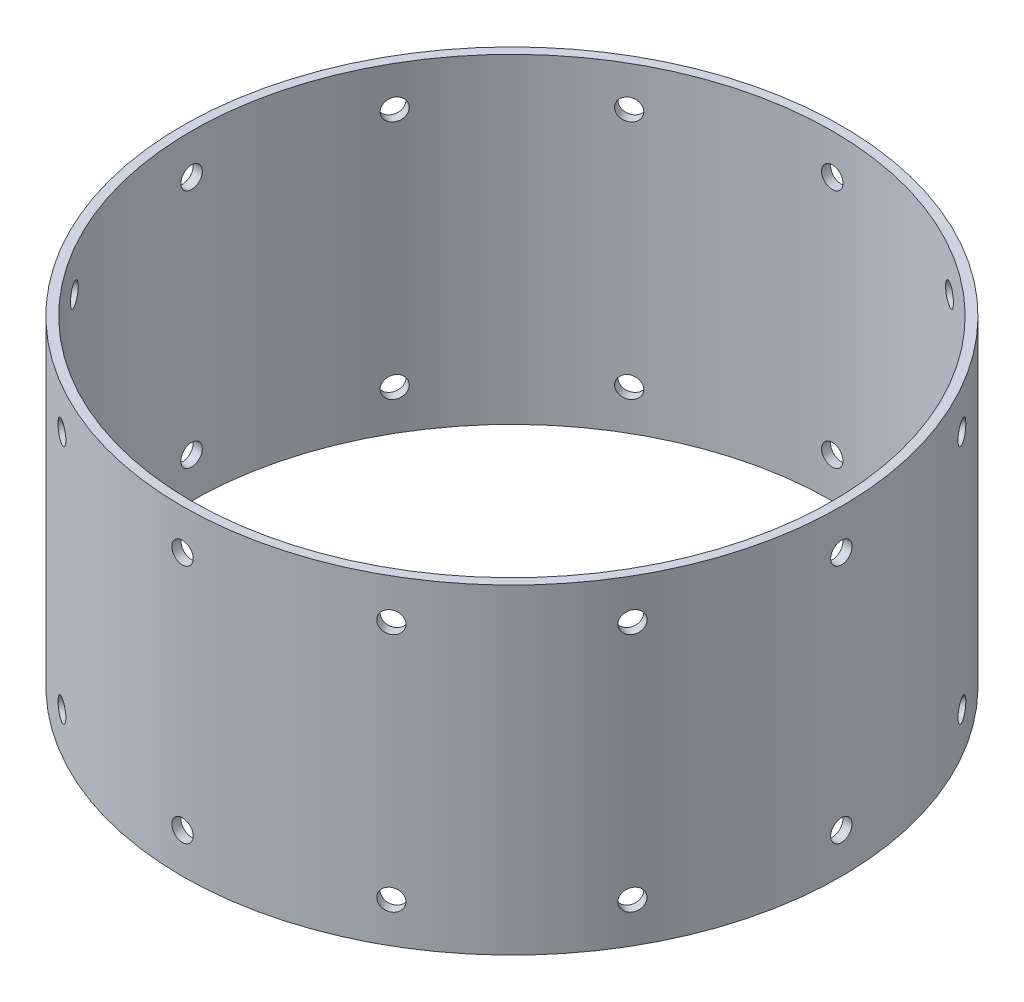
SolidWorks part; units mm, degrees
material "Fiberglass"
ref_plane "Front Plane" through (0, 0, 0) normal (0, 0, 1) x (1, 0, 0)
ref_plane "Top Plane" through (0, 0, 0) normal (0, 1, 0) x (1, 0, 0)
ref_plane "Right Plane" through (0, 0, 0) normal (1, 0, 0) x (0, 0, -1)
sketch "Sketch1" plane through (0, 0, 0) normal (0, 1, 0) x (1, 0, 0)
  circle A0 centre (0, 0) radius 76.2
  circle A1 centre (0, 0) radius 78.359
  dimension "D1" = 152.4
  dimension "D2" = 156.718
extrude "Boss-Extrude1" add sketch "Sketch1" along normal blind 76.2
sketch "Sketch2" plane through (0, 0, 0) normal (0, 0, 1) x (1, 0, 0)
  line L0 (0, 0) -> (0, 234.7266) construction
  line L1 (-76.2, 0) -> (76.2, 0) construction
  line L2 (-78.359, 0) -> (78.359, 0) construction
  line L3 (78.359, 38.1) -> (-54.7898, 38.1) construction
  line L4 (78.359, 0) -> (78.359, 76.2) construction
  circle A0 centre (0, 9.525) radius 2.54
  circle A1 centre (0, 66.675) radius 2.54
  dimension "D1" = 9.525
  dimension "D2" = 5.08
extrude "Cut-Extrude1" cut sketch "Sketch2" against normal through all
ref_axis "Axis1" through (0, 0, 0) along (0, 1, 0)
pattern_circular "CirPattern1" count 12 over 360 about axis through (0, 0, 0) along (0, 1, 0) of "Cut-Extrude1"
